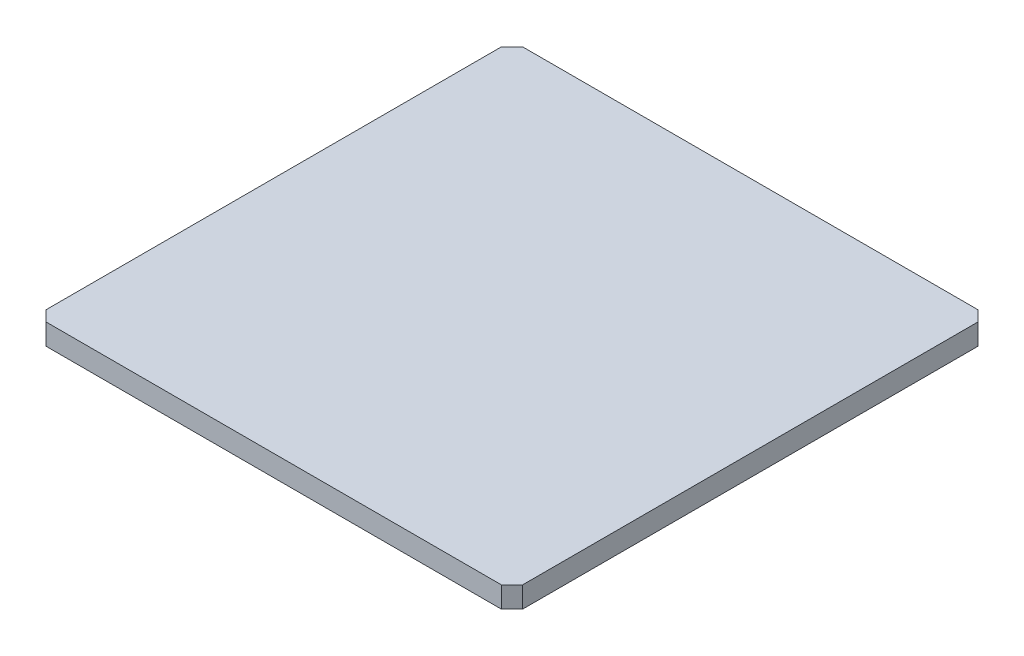
SolidWorks part; units mm, degrees
ref_plane "Front Plane" through (0, 0, 0) normal (0, 0, 1) x (1, 0, 0)
ref_plane "Top Plane" through (0, 0, 0) normal (0, 1, 0) x (1, 0, 0)
ref_plane "Right Plane" through (0, 0, 0) normal (1, 0, 0) x (0, 0, -1)
sketch "Sketch2" plane through (0, 0, 0) normal (0, 1, 0) x (1, 0, 0)
  line L1 (-56.5685, -56.5685) -> (56.5685, -56.5685)
  line L2 (-56.5685, -56.5685) -> (-56.5685, 56.5685)
  line L3 (-56.5685, 56.5685) -> (56.5685, 56.5685)
  line L4 (56.5685, -56.5685) -> (56.5685, 56.5685)
  line L5 (-56.5685, -56.5685) -> (56.5685, 56.5685) construction
  line L6 (-56.5685, 56.5685) -> (56.5685, -56.5685) construction
  point P0 (0, 0)
  dimension "D1" = 160
extrude "Boss-Extrude1" add sketch "Sketch2" along normal blind 5
chamfer "Chamfer1" distance 2.5 angle 45 4 edges at (-56.5685, 2.5, 56.5685) (56.5685, 2.5, 56.5685) (56.5685, 2.5, -56.5685) (-56.5685, 2.5, -56.5685)
